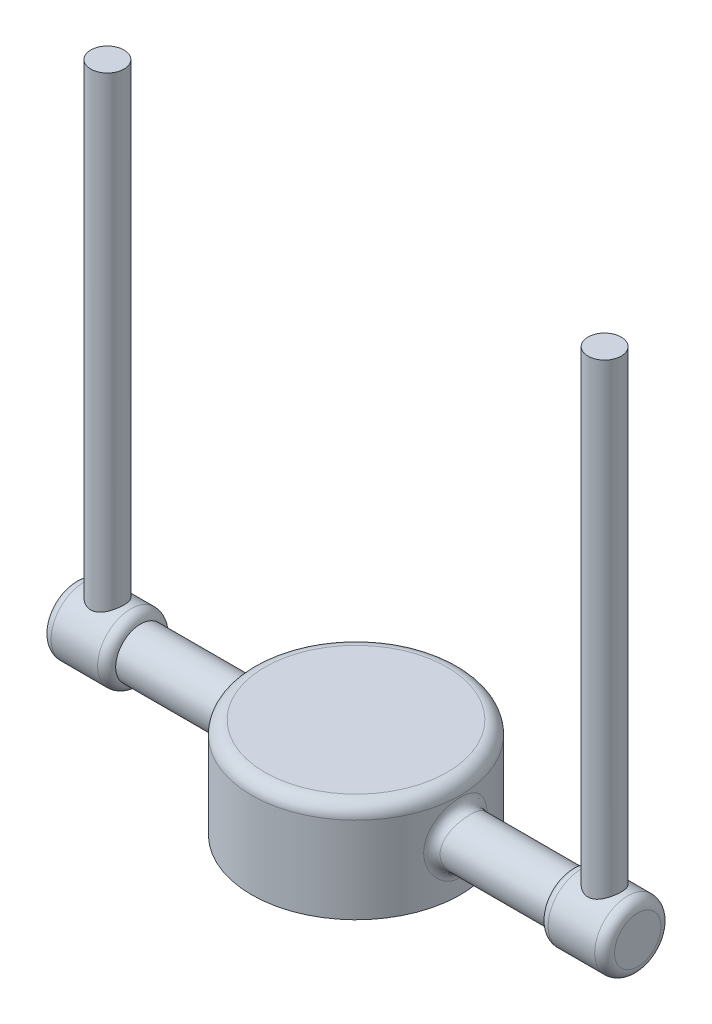
SolidWorks part; units mm, degrees
material "Polyester Resin"
ref_plane "Front Plane" through (0, 0, 0) normal (0, 0, 1) x (1, 0, 0)
ref_plane "Top Plane" through (0, 0, 0) normal (0, 1, 0) x (1, 0, 0)
ref_plane "Right Plane" through (0, 0, 0) normal (1, 0, 0) x (0, 0, -1)
sketch "Sketch1" plane through (0, 0, 0) normal (0, 1, 0) x (1, 0, 0)
  circle A0 centre (0, 0) radius 31.5
  dimension "D1" = 63
extrude "Boss-Extrude1" add sketch "Sketch1" along normal blind 30
sketch "Sketch2" plane through (0, 0, 0) normal (1, 0, 0) x (0, 0, -1)
  line L0 (0, 0) -> (0, 30) construction
  line L1 (31.5, 30) -> (-31.5, 30) construction
  circle A0 centre (0, 15) radius 7.5
  dimension "D1" = 15
extrude "Boss-Extrude2" add sketch "Sketch2" along normal blind 65
sketch "Sketch3" plane through (65, 0, 0) normal (1, 0, 0) x (0, 0, -1)
  circle A0 centre (0, 15) radius 10
  dimension "D1" = 20
extrude "Boss-Extrude3" add sketch "Sketch3" along normal blind 20
ref_axis "Axis1" through (0, 15, 0) along (1, 0, 0)
ref_plane "Plane1" through (0, 15, 0) normal (0, -1, 0) x (1, 0, 0)
sketch "Sketch4" plane through (0, 15, 0) normal (0, -1, 0) x (1, 0, 0)
  line L0 (0, 0) -> (65, 0) construction
  line L2 (65, 10) -> (65, -10) construction
  circle A0 centre (75, 0) radius 5
  dimension "D1" = 10
  dimension "D2" = 10
extrude "Boss-Extrude4" add sketch "Sketch4" against normal blind 150
fillet "Fillet1" radius 3 3 edges at (30.6305, 16.492, -7.3501) (65, 15, -10) (85, 15, -10)
mirror "Mirror1" about plane through (0, 0, 0) normal (1, 0, 0) of "Boss-Extrude3", "Boss-Extrude4", "Fillet1", "Boss-Extrude2"
fillet "Fillet2" radius 4 1 edges at (0, 30, 31.5)
